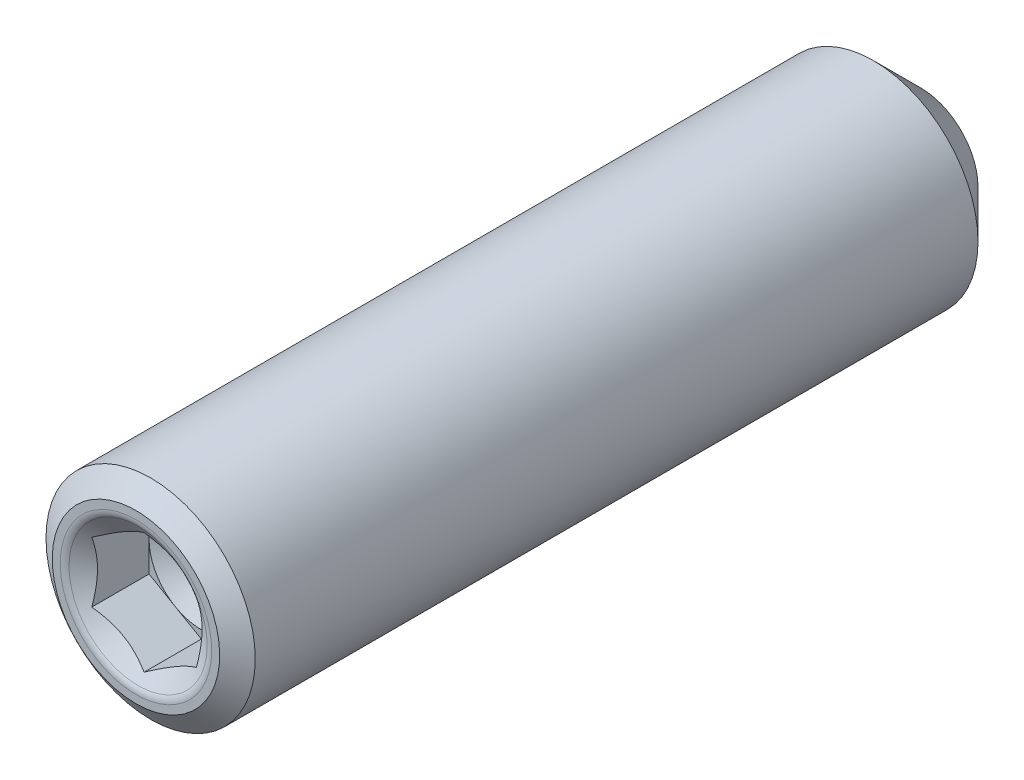
SolidWorks part; units mm, degrees
ref_plane "Front" through (0, 0, 0) normal (0, 0, 1) x (1, 0, 0)
ref_plane "Top" through (0, 0, 0) normal (0, 1, 0) x (1, 0, 0)
ref_plane "Right" through (0, 0, 0) normal (1, 0, 0) x (0, 0, -1)
sketch "Sketch22" plane through (0, 0, 0) normal (1, 0, 0) x (0, 0, -1)
  line L0 (-14.3415, 0) -> (-14.3415, 3.2)
  line L1 (-14.3415, 3.2) -> (-13.7813, 4)
  line L2 (-13.7813, 4) -> (13.8504, 4)
  line L3 (13.8504, 4) -> (15.6585, 2.1919)
  line L4 (15.6585, 2.1919) -> (14.3415, 0)
  line L5 (14.3415, 0) -> (-14.3415, 0)
  line L6 (14.3415, 0) -> (15.6585, 0) construction
  line L7 (15.6585, 0) -> (15.6585, 2.1919) construction
  line L8 (15.6585, -2.1919) -> (14.3415, 0) construction
  line L9 (-13.7813, -4) -> (13.8504, -4) construction
  dimension "Dia" = 8
  dimension "Length" = 30
  dimension "D3" = 35
  dimension "D5" = 118
  dimension "D6" = 45
  dimension "D7" = 6.4
revolve "Revolve1" add sketch "Sketch22" angle 360 about L6
ref_plane "Plane1" through (0, 0, -15.6585) normal (0, 0, 1) x (1, 0, 0)
sketch "Sketch27" plane through (0, 0, -15.6585) normal (0, 0, 1) x (1, 0, 0)
  circle A0 centre (0, 0) radius 4 construction
  circle A1 centre (0, 0) radius 4
curve "Helix/Spiral1" pitch 1.25 height 31.25 turns 25
sketch "Sketch28" plane through (0, 0, 0) normal (1, 0, 0) x (0, 0, -1)
  line L0 (15.6585, 4) -> (16.7523, 4)
  line L1 (16.7523, 4) -> (16.2835, 3.1881)
  line L2 (16.2835, 3.1881) -> (16.1273, 3.1881)
  line L3 (16.1273, 3.1881) -> (15.6585, 4)
  line L4 (15.8929, 3.5941) -> (16.5179, 3.5941) construction
  line L6 (-13.7813, 4) -> (13.8504, 4) construction
  dimension "D1" = 0.1562
  dimension "D2" = 0.625
  dimension "D3" = 60
sketch "Sketch23" plane through (0, 0, 14.3415) normal (0, 0, 1) x (1, 0, 0)
  line L1 (0, 2.3094) -> (-2, 1.1547)
  line L2 (-2, 1.1547) -> (-2, -1.1547)
  line L3 (-2, -1.1547) -> (0, -2.3094)
  line L4 (0, -2.3094) -> (2, -1.1547)
  line L5 (2, -1.1547) -> (2, 1.1547)
  line L6 (2, 1.1547) -> (0, 2.3094)
  circle A0 centre (0, 0) radius 2 construction
  dimension "Hex" = 4
extrude "Cut-Extrude10" cut sketch "Sketch23" against normal blind 2.5
sketch "Sketch24" plane through (0, 0, 14.3415) normal (0, 0, 1) x (1, 0, 0)
  line L0 (0, 2.3094) -> (0, 3.2) construction
  circle A0 centre (0, 0) radius 2.7547
  point P5 (0, 2.7547)
  dimension "D1" = 0.4453
extrude "Cut-Extrude11" cut sketch "Sketch24" against normal through all draft 55
sketch "Sketch26" plane through (0, 0, 11.8415) normal (0, 0, 1) x (1, 0, 0)
  circle A0 centre (0, 0) radius 2 construction
  circle A1 centre (0, 0) radius 2
extrude "Cut-Extrude12" cut sketch "Sketch26" against normal through all draft 60
sketch "Sketch30" plane through (0, 0, 0) normal (1, 0, 0) x (0, 0, -1)
  line L0 (-13.7813, 4) -> (13.8504, 4) construction
  line L1 (-14.3415, 0) -> (-14.3415, 3.2) construction
  line L2 (15.6585, 0) -> (15.6585, 2.1919) construction
  line L3 (-13.7813, -4) -> (13.8504, -4) construction
  point P0 (-14.3415, 4)
  point P1 (15.6585, 4)
  point P2 (15.6585, -4)
  point P11 (12.5335, -4)
  dimension "D1" = 3.125
sketch "Sketch31" plane through (0, 0, 0) normal (1, 0, 0) x (0, 0, -1)
  line L2 (14.3415, 0) -> (15.6585, -2.1919)
  line L3 (15.6585, 2.1919) -> (14.3415, 0)
fillet "Fillet2" radius 0.4453 1 edges at (2.7547, 0, 14.3415)
equation "\"D7@Sketch22\"=\"Dia@Sketch22\"*.8"
equation "\"D1@Sketch28\" = \"D4@Helix/Spiral1\" * .125"
equation "\"D2@Sketch28\" = \"D4@Helix/Spiral1\" * .5"
equation "\"D3@Helix/Spiral1\" = \"Length@Sketch22\" + \"D4@Helix/Spiral1\""
equation "\"D1@Sketch30\" = \"D4@Helix/Spiral1\" * 2.5"
equation "\"hex Depth@Cut-Extrude10\" = \"Hex@Sketch23\" * .625"
equation "\"D1@Fillet2\" = \"D1@Sketch24\""
